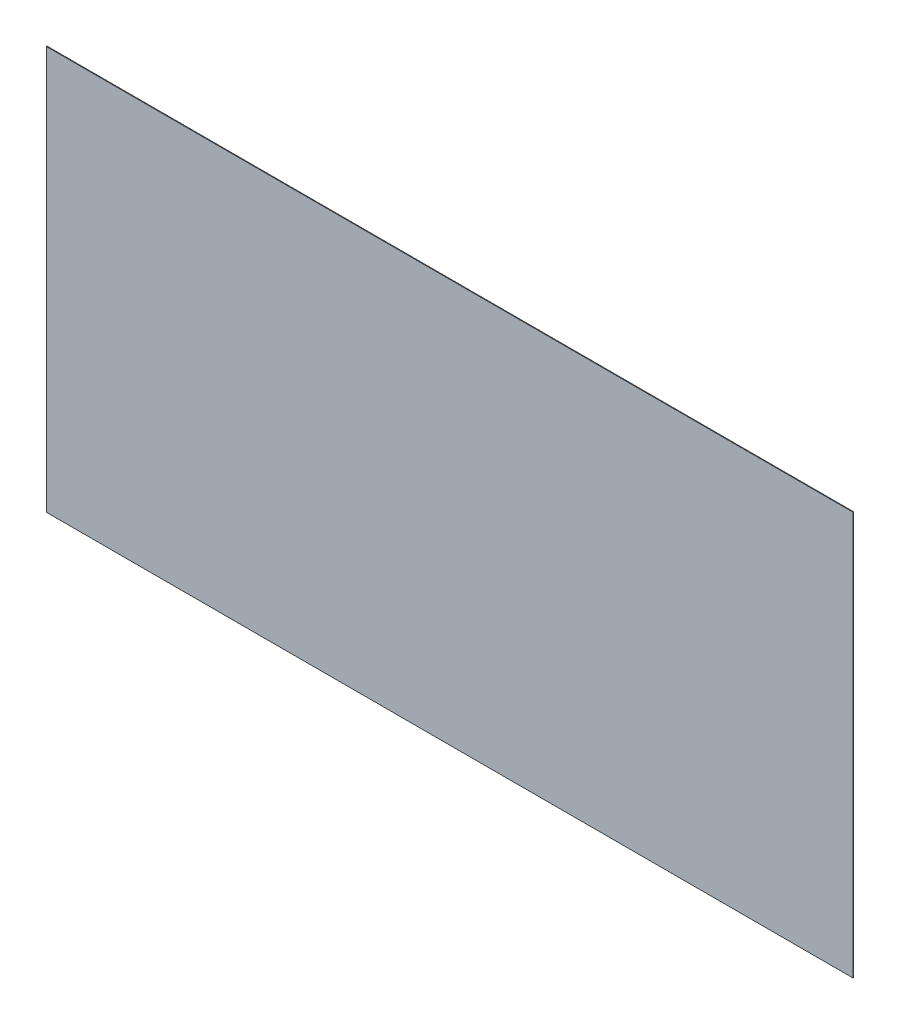
SolidWorks part; units mm, degrees
ref_plane "Front Plane" through (0, 0, 0) normal (0, 0, 1) x (1, 0, 0)
ref_plane "Top Plane" through (0, 0, 0) normal (0, 1, 0) x (1, 0, 0)
ref_plane "Right Plane" through (0, 0, 0) normal (1, 0, 0) x (0, 0, -1)
sketch "Sketch1" plane through (0, 0, 0) normal (0, 0, 1) x (1, 0, 0)
  line L1 (-914.4, -457.2) -> (914.4, -457.2)
  line L2 (-914.4, -457.2) -> (-914.4, 457.2)
  line L3 (-914.4, 457.2) -> (914.4, 457.2)
  line L4 (914.4, -457.2) -> (914.4, 457.2)
  line L5 (-914.4, -457.2) -> (914.4, 457.2) construction
  line L6 (-914.4, 457.2) -> (914.4, -457.2) construction
  point P0 (0, 0)
  dimension "D1" = 1828.8
  dimension "D2" = 914.4
extrude "Boss-Extrude1" add sketch "Sketch1" along normal blind 0.7937 and the other way blind 0.7937
